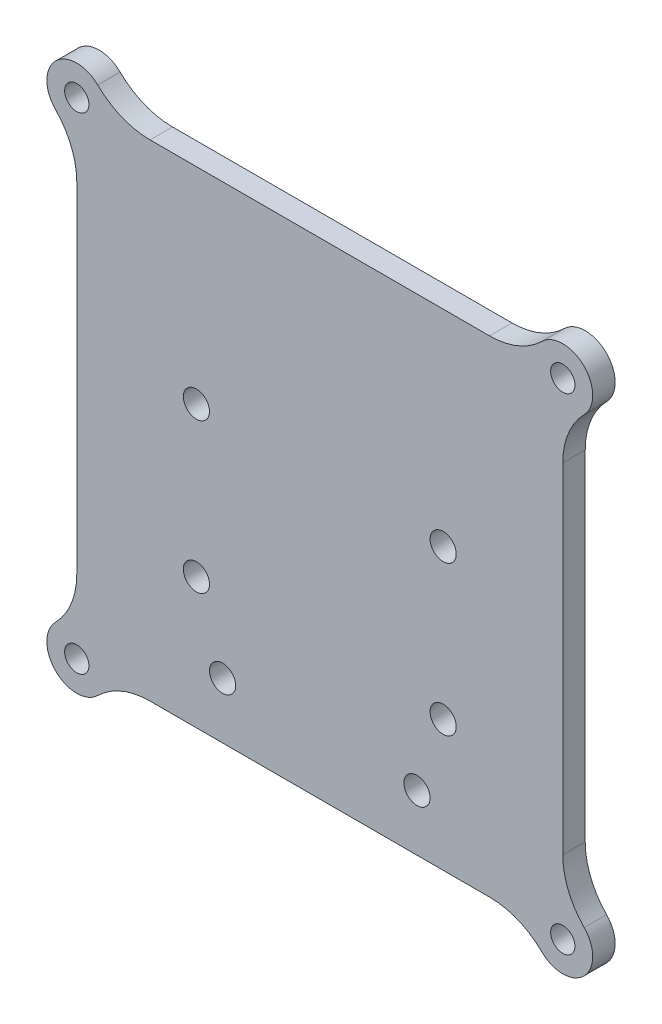
SolidWorks part; units mm, degrees
material "ABS"
ref_plane "Спереди" through (0, 0, 0) normal (0, 0, 1) x (1, 0, 0)
ref_plane "Сверху" through (0, 0, 0) normal (0, 1, 0) x (1, 0, 0)
ref_plane "Справа" through (0, 0, 0) normal (1, 0, 0) x (0, 0, -1)
sketch "Эскиз1" plane through (0, 0, 0) normal (0, 0, 1) x (1, 0, 0)
  line L1 (-32.5, -32.5) -> (32.5, -32.5)
  line L2 (-32.5, -32.5) -> (-32.5, 32.5)
  line L3 (-32.5, 32.5) -> (32.5, 32.5)
  line L4 (32.5, -32.5) -> (32.5, 32.5)
  line L5 (-32.5, -32.5) -> (32.5, 32.5) construction
  line L6 (-32.5, 32.5) -> (32.5, -32.5) construction
  circle A0 centre (-32.5, 32.5) radius 1.625
  arc A1 (-28.5, 32.5) -> (-32.5, 28.5) centre (-32.5, 32.5) ccw
  circle A2 centre (32.5, 32.5) radius 1.625
  arc A3 (32.5, 28.5) -> (28.5, 32.5) centre (32.5, 32.5) ccw
  circle A4 centre (32.5, -32.5) radius 1.625
  arc A5 (28.5, -32.5) -> (32.5, -28.5) centre (32.5, -32.5) ccw
  circle A6 centre (-32.5, -32.5) radius 1.625
  arc A7 (-32.5, -28.5) -> (-28.5, -32.5) centre (-32.5, -32.5) ccw
  point P0 (0, 0)
  point P20 (0, 0)
  dimension "D2" = 3.25
  dimension "D3" = 8
  dimension "D1" = 65
  dimension "D4" = 4
extrude "Бобышка-Вытянуть1" add sketch "Эскиз1" along normal blind 3 contours A6 L1 A4 L4 A2 L3 A0 L2 | L3 A1 L2 A0 | L4 A3 L3 A2 | L1 A5 L4 A4 | L2 A7 L1 A6 region at (0, 0, 0) region at (-29.6875, -32.6131, 0) region at (29.6875, -32.6131, 0) region at (-35.2484, 35.2484, 0) region at (32.6131, 29.6875, 0)
fillet "Скругление1" radius 10 8 edges at (-28.5, -32.5, 1.5) (-32.5, -28.5, 1.5) (-28.5, 32.5, 1.5) (-32.5, 28.5, 1.5) (28.5, 32.5, 1.5) (32.5, 28.5, 1.5) (32.5, -28.5, 1.5) (28.5, -32.5, 1.5)
sketch "Эскиз2" plane through (0, 0, 3) normal (0, 0, 1) x (1, 0, 0)
  line L0 (0, 32.5) -> (0, -32.5) construction
  line L1 (-22.702, 32.5) -> (22.702, 32.5) construction
  line L2 (-22.702, -32.5) -> (22.702, -32.5) construction
  line L3 (-15.6432, -25) -> (20.4381, -25) construction
  circle A0 centre (-13, -25) radius 1.75
  circle A1 centre (13, -25) radius 1.75
  dimension "D1" = 3.5
  dimension "D2" = 13
  dimension "D3" = 7.5
sketch "Эскиз3" plane through (0, 0, 3) normal (0, 0, 1) x (1, 0, 0)
  circle A0 centre (0, 0) radius 50
  dimension "D1" = 100
extrude "Вырез-Вытянуть1" cut sketch "Эскиз2" against normal blind 10
sketch "Эскиз4" plane through (0, 0, 3) normal (0, 0, 1) x (1, 0, 0)
  line L0 (0, -32.5) -> (0, 32.5) construction
  line L1 (-22.702, -32.5) -> (22.702, -32.5) construction
  line L2 (-22.702, 32.5) -> (22.702, 32.5) construction
  line L3 (-22.6055, -15) -> (24.9146, -15) construction
  circle A0 centre (-16.5, -15) radius 1.75
  circle A1 centre (16.5, -15) radius 1.75
  dimension "D1" = 3.5
  dimension "D2" = 16.5
  dimension "D3" = 17.5
extrude "Вырез-Вытянуть2" cut sketch "Эскиз4" against normal blind 10
sketch "Эскиз5" plane through (0, 0, 3) normal (0, 0, 1) x (1, 0, 0)
  line L0 (-32.5, 5) -> (32.5, 5) construction
  line L1 (-32.5, -22.702) -> (-32.5, 22.702) construction
  line L2 (32.5, -22.702) -> (32.5, 22.702) construction
  line L3 (0, -32.5) -> (0, 32.5) construction
  line L4 (-22.702, -32.5) -> (22.702, -32.5) construction
  line L5 (-22.702, 32.5) -> (22.702, 32.5) construction
  circle A0 centre (-16.5, 5) radius 1.75
  circle A1 centre (16.5, 5) radius 1.75
  dimension "D1" = 3.5
  dimension "D2" = 16.5
  dimension "D3" = 37.5
extrude "Вырез-Вытянуть3" cut sketch "Эскиз5" against normal blind 10
